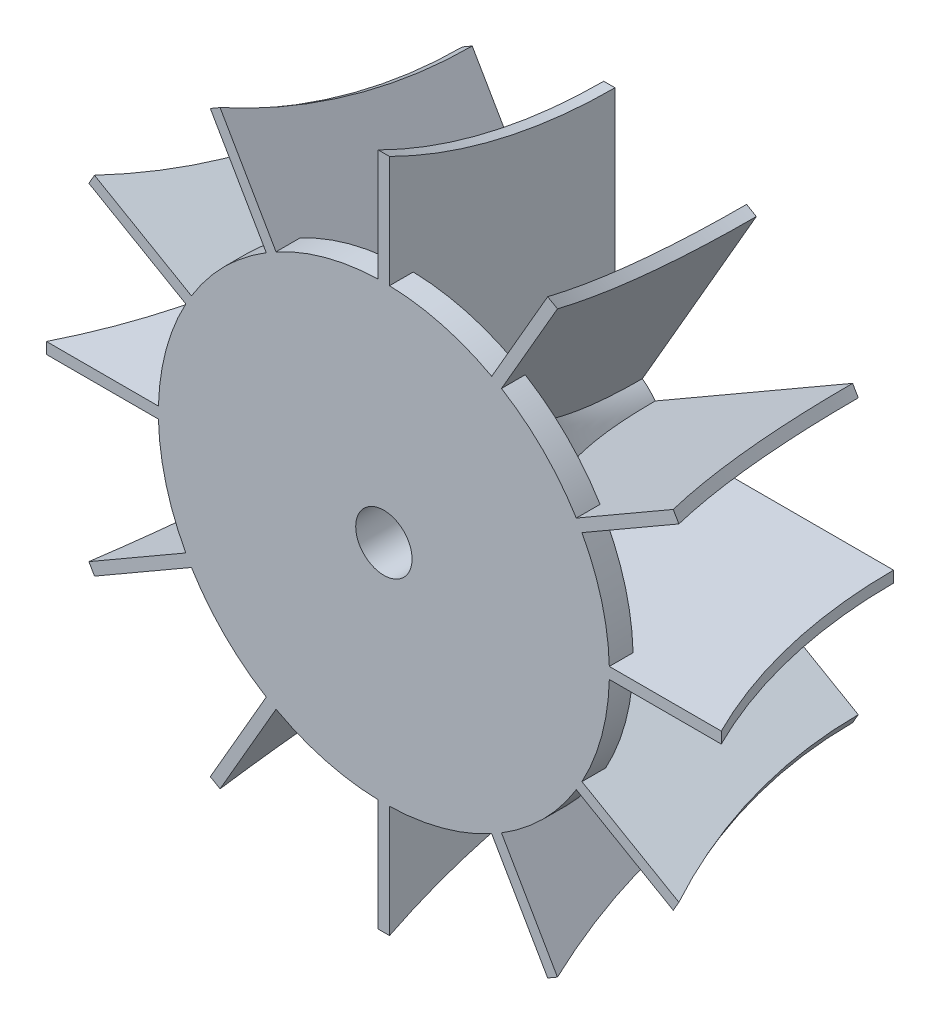
SolidWorks part; units mm, degrees
ref_plane "Front Plane" through (0, 0, 0) normal (0, 0, 1) x (1, 0, 0)
ref_plane "Top Plane" through (0, 0, 0) normal (0, 1, 0) x (1, 0, 0)
ref_plane "Right Plane" through (0, 0, 0) normal (1, 0, 0) x (0, 0, -1)
sketch "Sketch1" plane through (0, 0, 0) normal (0, 1, 0) x (1, 0, 0)
  line L0 (0, 0) -> (25.4, 0)
  line L1 (25.4, 0) -> (25.4, 2.6751)
  line L2 (6.35, 25.4) -> (0, 25.4)
  line L3 (0, 25.4) -> (0, 0)
  line L4 (6.35, 25.4) -> (6.35, 35.5003) construction
  arc A0 (25.4, 2.6751) -> (6.35, 25.4) centre (29.4293, 25.4) cw
  point P6 (6.35, 35.5461)
  point P8 (25.4, 4.4466)
  point P10 (25.4, 6.35)
  point P11 (25.4, 6.35)
  point P12 (25.4, 2.6751)
  dimension "D1" = 25.4
  dimension "D2" = 6.35
  dimension "D3" = 25.4
revolve "Revolve1" add sketch "Sketch1" angle 360 about L3
sketch "Sketch2" plane through (0, 0, -25.4) normal (0, 0, -1) x (-1, 0, 0)
  circle A0 centre (0, 0) radius 3.175
  dimension "D1" = 6.35
extrude "Cut-Extrude1" cut sketch "Sketch2" against normal through all
sketch "Sketch4" plane through (0, 0, 0) normal (1, 0, 0) x (0, 0, -1)
  line L0 (25.4, -6.35) -> (25.4, 6.35) construction
  line L1 (0, 25.4) -> (0, -25.4) construction
  line L2 (25.4, -32) -> (63.8866, -32) construction
  line L3 (0, -38) -> (0, -22.679)
  line L4 (0, -22.679) -> (6.6423, -9.5856)
  line L5 (6.6423, -9.5856) -> (25.4, -4.782)
  line L6 (25.4, -4.782) -> (25.4, -32)
  arc A1 (0, -38) -> (25.4, -32) centre (25.4, -88.7633) cw
  point P3 (25.4, -4.782)
  dimension "D1" = 38
  dimension "D2" = 32
extrude "Boss-Extrude1" add sketch "Sketch4" along normal mid plane 1.27
pattern_circular "CirPattern1" count 12 over 360 about axis through (0, 0, -25.4) along (0, 0, -1) of "Boss-Extrude1"
